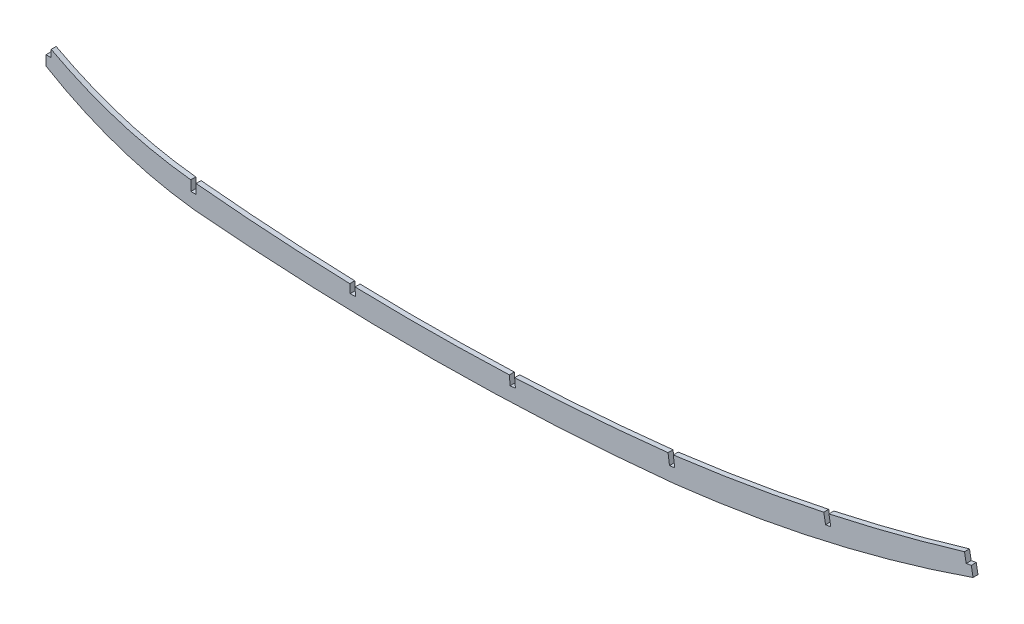
SolidWorks part; units mm, degrees
material "Balsa"
ref_plane "Front Plane" through (0, 0, 0) normal (0, 0, 1) x (1, 0, 0)
ref_plane "Top Plane" through (0, 0, 0) normal (0, 1, 0) x (1, 0, 0)
ref_plane "Right Plane" through (0, 0, 0) normal (1, 0, 0) x (0, 0, -1)
sketch "Sketch2" plane through (0, 0, 0) normal (0, 0, 1) x (1, 0, 0)
  line L0 (0, -94.4694) -> (0, -81.7694)
  line L1 (0, -94.4694) -> (93.98, -94.4694) construction
  line L2 (93.98, -126.4975) -> (93.98, -111.2575) construction
  line L3 (349.6407, -137.6462) -> (348.9613, -137.618) construction
  line L4 (349.6407, -137.6462) -> (354.8905, -137.8645) construction
  line L5 (93.98, -94.4694) -> (93.98, -126.4975) construction
  line L6 (400.2036, -124.7658) -> (400.2036, -94.4694) construction
  line L7 (590.8643, -81.3536) -> (588.5933, -68.8583)
  line L8 (0, 0) -> (672.417, 0) construction
  line L10 (93.98, -94.4694) -> (590.8643, -94.4694) construction
  line L11 (590.8643, -94.4694) -> (590.8643, -81.3536) construction
  line L12 (400.2036, -124.7658) -> (396.2207, -94.4694) construction
  arc A0 (0, -94.4694) -> (93.98, -126.4975) centre (121.7349, 108.8411) ccw
  arc A3 (93.98, -126.4975) -> (400.2036, -124.7658) centre (237.9716, 1487.1243) ccw
  arc A6 (400.2036, -124.7658) -> (590.8643, -81.3536) centre (300.4984, 753.5129) ccw
  arc A7 (93.98, -111.2575) -> (398.1841, -109.4039) centre (237.3586, 1321.3743) ccw
  arc A10 (0, -81.7694) -> (93.98, -111.2575) centre (118.1544, 130.2915) ccw
  arc A11 (398.1841, -109.4039) -> (588.5933, -68.8583) centre (254.6725, 1031.9221) ccw
  dimension "D3" = 236.9696
  dimension "D4" = 30.2963
  dimension "D5" = 400.2036
  dimension "D6" = 79.699
  dimension "D7" = 82.511
  dimension "D8" = 15.24
  dimension "D11" = 242.7557
  dimension "D14" = 1620.0336
  dimension "D15" = 883.92
  dimension "D16" = 15.494
  dimension "D18" = 1150.3133
  dimension "D1" = 12.7
  dimension "D2" = 81.7694
  dimension "D9" = 32.028
  dimension "D10" = 93.98
  dimension "D12" = 13.1158
  dimension "D13" = 496.8843
  dimension "D17" = 12.7
extrude "Boss-Extrude1" add sketch "Sketch2" along normal blind 3.175 contours A11 A7 A10 L0 A0 A3 A6 region at (5.9433, -88.1194, 0)
sketch "Sketch3" plane through (0, 0, 3.175) normal (0, 0, 1) x (1, 0, 0)
  line L0 (0, 0) -> (0, -81.8237) construction
  line L1 (0, 0) -> (93.98, 0) construction
  line L2 (93.98, 0) -> (93.98, -117.6075) construction
  line L4 (0, -81.8237) -> (0, -88.1813)
  line L5 (0, -88.1813) -> (3.302, -88.1813)
  line L6 (3.302, -81.8237) -> (3.302, -88.1813)
  line L7 (193.9543, -123.223) -> (197.1266, -123.0902)
  line L8 (0, -81.8237) -> (0, -80.8493)
  line L9 (0, -80.8493) -> (3.302, -80.8493)
  line L10 (3.302, -80.8493) -> (3.302, -81.8237)
  line L11 (186.3309, 134.7479) -> (183.1587, 134.6151)
  line L12 (92.2909, -117.5313) -> (95.6691, -117.5313)
  line L13 (92.2909, -117.5313) -> (92.2909, -108.4147)
  line L14 (92.2909, -108.4147) -> (95.6691, -108.4147)
  line L15 (95.6691, -117.5313) -> (95.6691, -108.4147)
  line L16 (193.687, -116.8375) -> (196.8592, -116.7047)
  line L17 (186.5983, 128.3624) -> (183.4261, 128.2296)
  line L18 (197.1266, -123.0902) -> (196.8592, -116.7047)
  line L19 (186.5983, 128.3624) -> (186.3309, 134.7479)
  line L20 (193.9543, -123.223) -> (193.687, -116.8375)
  line L21 (183.4261, 128.2296) -> (183.1587, 134.6151)
  line L22 (183.4261, 128.2296) -> (183.1587, 134.6151)
  line L24 (186.5983, 128.3624) -> (186.3309, 134.7479)
  line L26 (186.5983, 128.3624) -> (183.4261, 128.2296)
  line L28 (186.3309, 134.7479) -> (183.1587, 134.6151)
  line L30 (195.5404, -123.1566) -> (190.3839, 0) construction
  line L31 (93.98, 0) -> (612.4013, 0) construction
  line L32 (574.4157, 0) -> (588.1634, -75.3909) construction
  line L33 (193.8496, -123.1511) -> (197.2249, -123.0098)
  line L34 (193.8496, -123.1511) -> (193.5511, -116.0212)
  line L35 (197.2249, -123.0098) -> (196.9263, -115.8799)
  line L36 (193.5511, -116.0212) -> (196.9263, -115.8799)
  line L37 (397.3751, -116.2998) -> (400.7239, -115.855)
  line L38 (397.3751, -116.2998) -> (395.8625, -104.9127)
  line L39 (286.9301, 0) -> (297.4996, -122.788) construction
  line L40 (295.8233, -123.0088) -> (299.189, -122.7191)
  line L41 (295.8233, -123.0088) -> (295.1616, -115.3225)
  line L42 (299.189, -122.7191) -> (298.5274, -115.0328)
  line L43 (295.1616, -115.3225) -> (298.5274, -115.0328)
  line L44 (383.6307, 0) -> (399.0395, -116.0018) construction
  line L45 (400.7239, -115.855) -> (399.2113, -104.4679)
  line L46 (395.8625, -104.9127) -> (399.2113, -104.4679)
  line L48 (586.5153, -75.7689) -> (589.8387, -75.1629)
  line L49 (480.4996, 0) -> (498.5238, -98.843) construction
  line L50 (496.8758, -99.221) -> (500.1992, -98.615)
  line L51 (496.8758, -99.221) -> (495.4086, -91.1748)
  line L52 (500.1992, -98.615) -> (498.732, -90.5688)
  line L53 (495.4086, -91.1748) -> (498.732, -90.5688)
  line L56 (586.5153, -75.7689) -> (585.2098, -68.6095)
  line L57 (589.8387, -75.1629) -> (588.5332, -68.0035)
  line L58 (585.2098, -68.6095) -> (588.5332, -68.0035)
  point P14 (93.98, -108.4147)
  point P25 (195.2387, -115.9505)
  point P28 (297.5062, -122.864)
  point P31 (399.0495, -116.0774)
  point P39 (498.5375, -98.918)
  point P44 (0, 0)
  point P51 (588.177, -75.4659)
  dimension "D1" = 81.8237
  dimension "D2" = 6.3576
  dimension "D3" = 3.302
  dimension "D4" = 93.98
  dimension "D5" = 117.6075
  dimension "D6" = 3.3782
  dimension "D7" = 0.0762
  dimension "D8" = 92.398
  dimension "D9" = 0.0762
  dimension "D10" = 3.3782
  dimension "D11" = 190.3839
  dimension "D12" = 123.2645
  dimension "D13" = 94.92
  dimension "D14" = 96.5461
  dimension "D15" = 123.2421
  dimension "D16" = 0.0762
  dimension "D17" = 3.3782
  dimension "D18" = 96.7007
  dimension "D19" = 97.566
  dimension "D20" = 117.0207
  dimension "D21" = 0.0762
  dimension "D22" = 3.3782
  dimension "D23" = 96.8689
  dimension "D24" = 100.334
  dimension "D25" = 100.473
  dimension "D26" = 3.3782
  dimension "D27" = 0.0762
  dimension "D28" = 93.9161
  dimension "D29" = 76.6341
  dimension "D30" = 100.334
  dimension "D31" = 0.0762
  dimension "D32" = 3.3782
extrude "Cut-Extrude2" cut sketch "Sketch3" against normal through all
